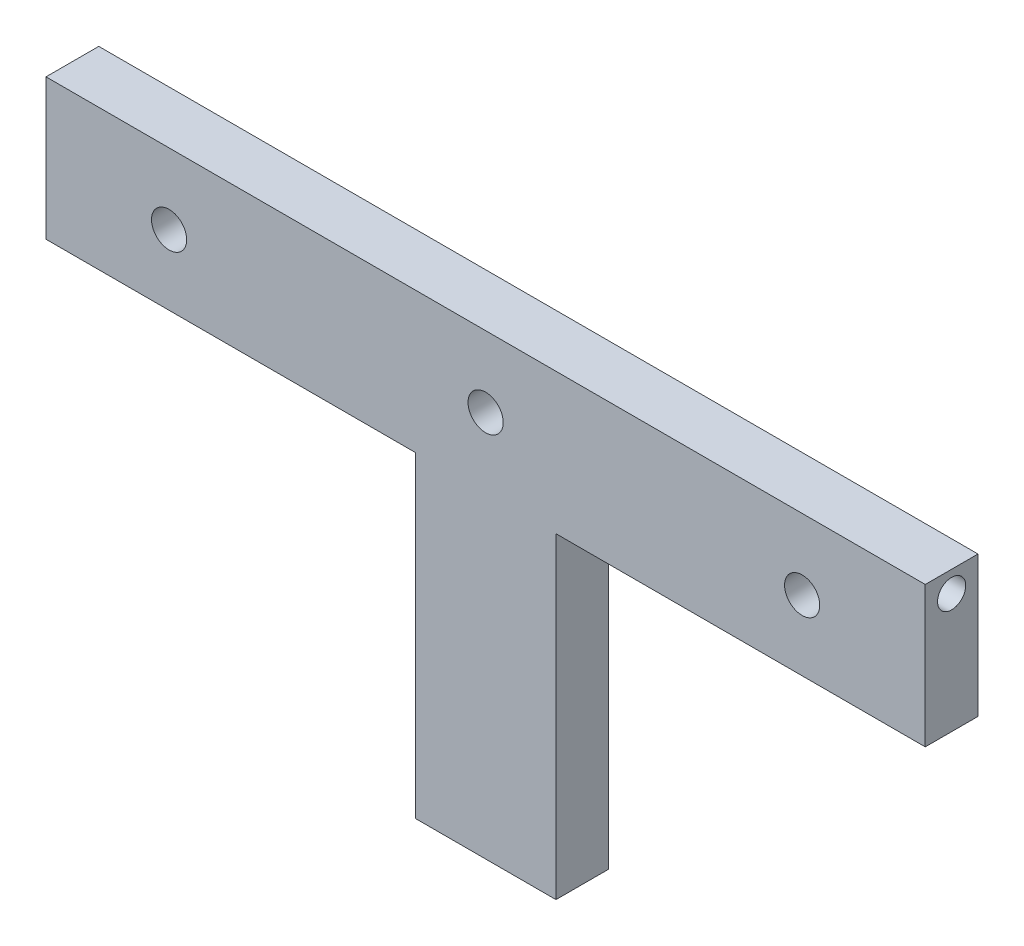
SolidWorks part; units mm, degrees
ref_plane "前基準面" through (0, 0, 0) normal (0, 0, 1) x (1, 0, 0)
ref_plane "上基準面" through (0, 0, 0) normal (0, 1, 0) x (1, 0, 0)
ref_plane "右基準面" through (0, 0, 0) normal (1, 0, 0) x (0, 0, -1)
sketch "草圖1" plane through (0, 0, 0) normal (0, 0, 1) x (1, 0, 0)
  line L0 (-15.1551, 7.2196) -> (-55.1551, 7.2196)
  line L1 (-55.1551, 7.2196) -> (-55.1551, 97.3297)
  line L2 (-55.1551, 97.3297) -> (-160.1551, 97.3297)
  line L3 (-160.1551, 97.3297) -> (-160.1551, 137.3297)
  line L4 (-160.1551, 137.3297) -> (89.8449, 137.3297)
  line L5 (89.8449, 137.3297) -> (89.8449, 97.3297)
  line L6 (89.8449, 97.3297) -> (-15.1551, 97.3297)
  line L7 (-15.1551, 97.3297) -> (-15.1551, 7.2196)
  line L8 (-35.1551, 137.3297) -> (-35.1551, 151.4898) construction
  line L9 (-35.1551, 7.2196) -> (-35.1551, -12.7977) construction
  dimension "D1" = 250
  dimension "D2" = 40
  dimension "D3" = 40
extrude "填料-伸長1" add sketch "草圖1" along normal blind 15
sketch "草圖2" plane through (0, 0, 15) normal (0, 0, 1) x (1, 0, 0)
  line L0 (89.8449, 97.3297) -> (89.8449, 137.3297) construction
  circle A0 centre (54.8449, 117.1895) radius 5
  circle A1 centre (-35.1551, 117.1895) radius 5
  circle A2 centre (-125.1551, 117.1895) radius 5
  dimension "D1" = 10
  dimension "D2" = 10
  dimension "D3" = 10
  dimension "D4" = 90
  dimension "D5" = 90
  dimension "D6" = 35
extrude "除料-伸長1" cut sketch "草圖2" against normal through all
sketch "草圖3" plane through (89.8449, 0, 0) normal (1, 0, 0) x (0, 0, -1)
  line L0 (0, 97.3297) -> (0, 137.3297) construction
  line L1 (-15, 137.3297) -> (0, 137.3297) construction
  circle A0 centre (-7.5, 131.3297) radius 4
  dimension "D1" = 8
  dimension "D2" = 7.5
  dimension "D3" = 6
extrude "除料-伸長2" cut sketch "草圖3" against normal through all
